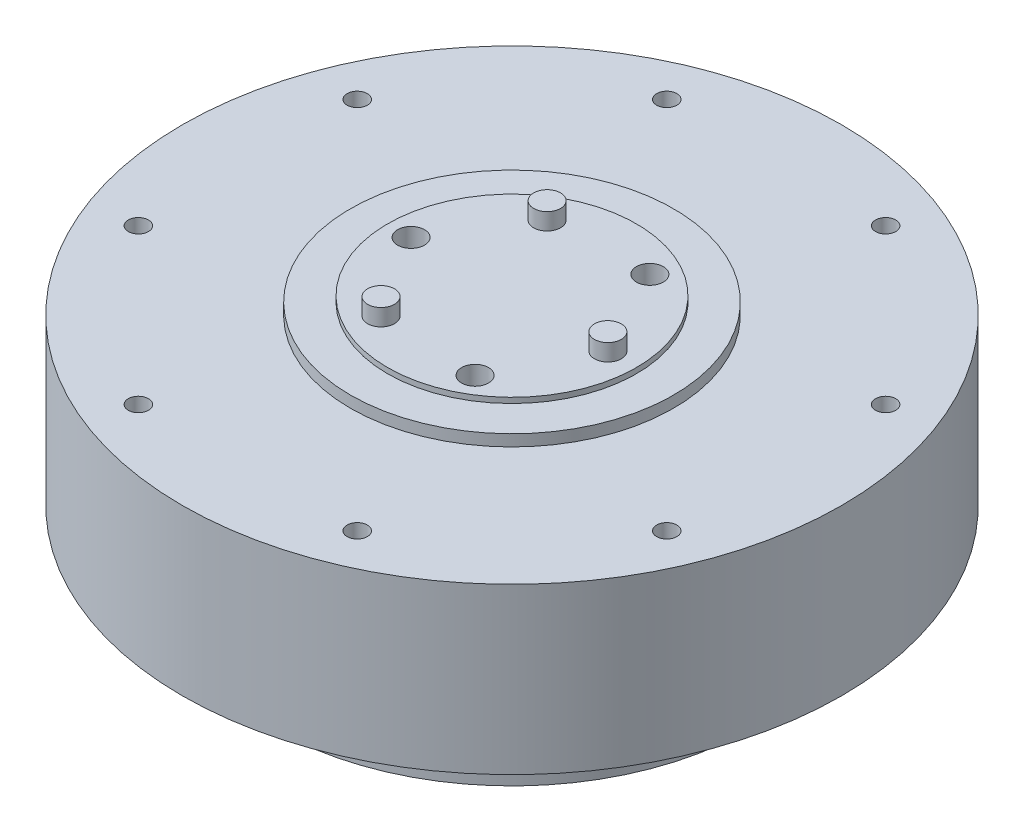
SolidWorks part; units mm, degrees
ref_plane "Front Plane" through (0, 0, 0) normal (0, 0, 1) x (1, 0, 0)
ref_plane "Top Plane" through (0, 0, 0) normal (0, 1, 0) x (1, 0, 0)
ref_plane "Right Plane" through (0, 0, 0) normal (1, 0, 0) x (0, 0, -1)
sketch "Sketch1" plane through (0, 0, 0) normal (0, 1, 0) x (1, 0, 0)
  circle A0 centre (0, 0) radius 49
  dimension "D1" = 98
extrude "Boss-Extrude1" add sketch "Sketch1" along normal blind 24.5
sketch "Sketch2" plane through (0, 24.5, 0) normal (0, 1, 0) x (1, 0, 0)
  circle A0 centre (0, 0) radius 24
  dimension "D1" = 48
extrude "Boss-Extrude2" add sketch "Sketch2" along normal blind 1.7
sketch "Sketch3" plane through (0, 26.2, 0) normal (0, 1, 0) x (1, 0, 0)
  circle A0 centre (0, 0) radius 18.5
  dimension "D1" = 37
extrude "Boss-Extrude3" add sketch "Sketch3" along normal blind 0.8
sketch "Sketch4" plane through (0, 0, 0) normal (0, -1, 0) x (1, 0, 0)
  circle A0 centre (0, 0) radius 35.5
  dimension "D1" = 71
extrude "Boss-Extrude4" add sketch "Sketch4" along normal blind 11
sketch "Sketch5" [suppressed] plane through (0, -11, 0) normal (0, -1, 0) x (1, 0, 0)
  line L0 (-33.5575, 11.5821) -> (33.5575, -11.5821) construction
  line L1 (-32.7234, 13.7634) -> (-28.0793, 12.1605)
  line L2 (-34.4168, 8.7024) -> (-29.7794, 7.1535)
  circle A0 centre (0, 0) radius 35.5 construction
  arc A1 (-32.7234, 13.7634) -> (-34.4168, 8.7024) centre (0, 0) ccw
  arc A2 (-29.7794, 7.1535) -> (-28.0793, 12.1605) centre (-28.9419, 9.6612) ccw
hole_wizard "Ø3.0mm Dowel Hole1" positions "Sketch12" profile "Sketch13" hole size "Ø3.0" standard "ANSI Metric"
sketch "Sketch12" plane through (0, 0, 0) normal (0, -1, 0) x (-1, 0, 0)
  line L0 (0, 0) -> (61.812, 0) construction
  line L2 (0, 0) -> (39.2649, -16.264) construction
  circle A0 centre (0, 0) radius 42.5 construction
  point P0 (39.2649, -16.264)
  dimension "D1" = 85
  dimension "D2" = 22.5
sketch "Sketch13" plane through (-39.2649, 0, 16.264) normal (1, 0, 0) x (0, 0, -1)
  line L0 (0, 0) -> (0, 3.9013)
  line L1 (0, 3.9013) -> (1.5, 3)
  line L2 (1.5, 3) -> (1.5, 0)
  line L5 (1.5, 0) -> (0, 0)
  line L10 (0, 3.9013) -> (-1.5, 3) construction
  line L11 (0, -6.35) -> (0, 107.95) construction
  dimension "Hole Dia." = 3
  dimension "Hole Depth" = 3
  dimension "Drill Angle" = 118
ref_axis "Axis1" through (0, -12.925, 0) along (0, 1, 0)
pattern_circular "CirPattern1" count 8 over 360 about axis through (0, -12.925, 0) along (0, 1, 0) of "Ø3.0mm Dowel Hole1"
hole_wizard "Ø4.0mm Dowel Hole1" positions "Sketch14" profile "Sketch15" hole size "Ø4.0" standard "ANSI Metric"
sketch "Sketch14" plane through (0, 27, 0) normal (0, 1, 0) x (1, 0, 0)
  circle A0 centre (0, 0) radius 15 construction
  point P0 (-15, 0)
  dimension "D1" = 30
sketch "Sketch15" plane through (-15, 27, 0) normal (1, 0, 0) x (0, 0, 1)
  line L0 (0, 0) -> (0, 5.7017)
  line L1 (0, 5.7017) -> (2, 4.5)
  line L2 (2, 4.5) -> (2, 0)
  line L5 (2, 0) -> (0, 0)
  line L10 (0, 5.7017) -> (-2, 4.5) construction
  line L11 (0, -6.35) -> (0, 107.95) construction
  dimension "Hole Dia." = 4
  dimension "Hole Depth" = 4.5
  dimension "Drill Angle" = 118
pattern_circular "CirPattern2" count 6 every 60 about axis through (0, -12.925, 0) along (0, 1, 0) skipping 1, 3, 5 of "Ø4.0mm Dowel Hole1"
sketch "Sketch20" plane through (0, 24.5, 0) normal (0, 1, 0) x (1, 0, 0)
  circle A0 centre (39.2649, -16.264) radius 1.5 construction
  circle A1 centre (16.264, -39.2649) radius 1.5 construction
  circle A2 centre (-16.264, -39.2649) radius 1.5 construction
  circle A3 centre (-39.2649, -16.264) radius 1.5 construction
  circle A4 centre (-39.2649, 16.264) radius 1.5 construction
  circle A5 centre (-16.264, 39.2649) radius 1.5 construction
  circle A6 centre (16.264, 39.2649) radius 1.5 construction
  circle A7 centre (39.2649, 16.264) radius 1.5 construction
  circle A8 centre (39.2649, -16.264) radius 1.5
  circle A9 centre (16.264, -39.2649) radius 1.5
  circle A10 centre (-16.264, -39.2649) radius 1.5
  circle A11 centre (-39.2649, -16.264) radius 1.5
  circle A12 centre (-39.2649, 16.264) radius 1.5
  circle A13 centre (-16.264, 39.2649) radius 1.5
  circle A14 centre (16.264, 39.2649) radius 1.5
  circle A15 centre (39.2649, 16.264) radius 1.5
extrude "Cut-Extrude1" cut sketch "Sketch20" against normal blind 3.5
sketch "Sketch21" plane through (0, 27, 0) normal (0, 1, 0) x (1, 0, 0)
  line L0 (-7.125, 12.3409) -> (0, 0) construction
  line L1 (0, 0) -> (-15, 0) construction
  circle A0 centre (-7.125, 12.3409) radius 2
  dimension "D1" = 4
  dimension "D2" = 14.25
  dimension "D3" = 60
extrude "Boss-Extrude5" add sketch "Sketch21" along normal blind 2.5
pattern_circular "CirPattern3" count 3 every 120 about axis through (0, 27, 0) along (0, 1, 0) of "Boss-Extrude5"
sketch "Sketch25" [suppressed] plane through (0, 27.5, 0) normal (0, 1, 0) x (1, 0, 0)
  line L0 (-7, 12.1244) -> (0, 0) construction
  line L1 (0, 0) -> (-7, -12.1244) construction
  line L2 (0, 0) -> (14, 0) construction
  circle A0 centre (-7, 12.1244) radius 2
  circle A1 centre (-7, -12.1244) radius 2
  circle A2 centre (14, 0) radius 2
  dimension "D1" = 4
  dimension "D2" = 4
  dimension "D3" = 4
  dimension "D4" = 120
  dimension "D5" = 120
  dimension "D6" = 14
extrude "Cut-Extrude2" [suppressed] cut sketch "Sketch25" against normal blind 2.5
equation "\"D2@Sketch25\"=\"D1@Sketch25\""
equation "\"D3@Sketch25\"=\"D1@Sketch25\""
equation "\"D5@Sketch25\"=\"D4@Sketch25\""
